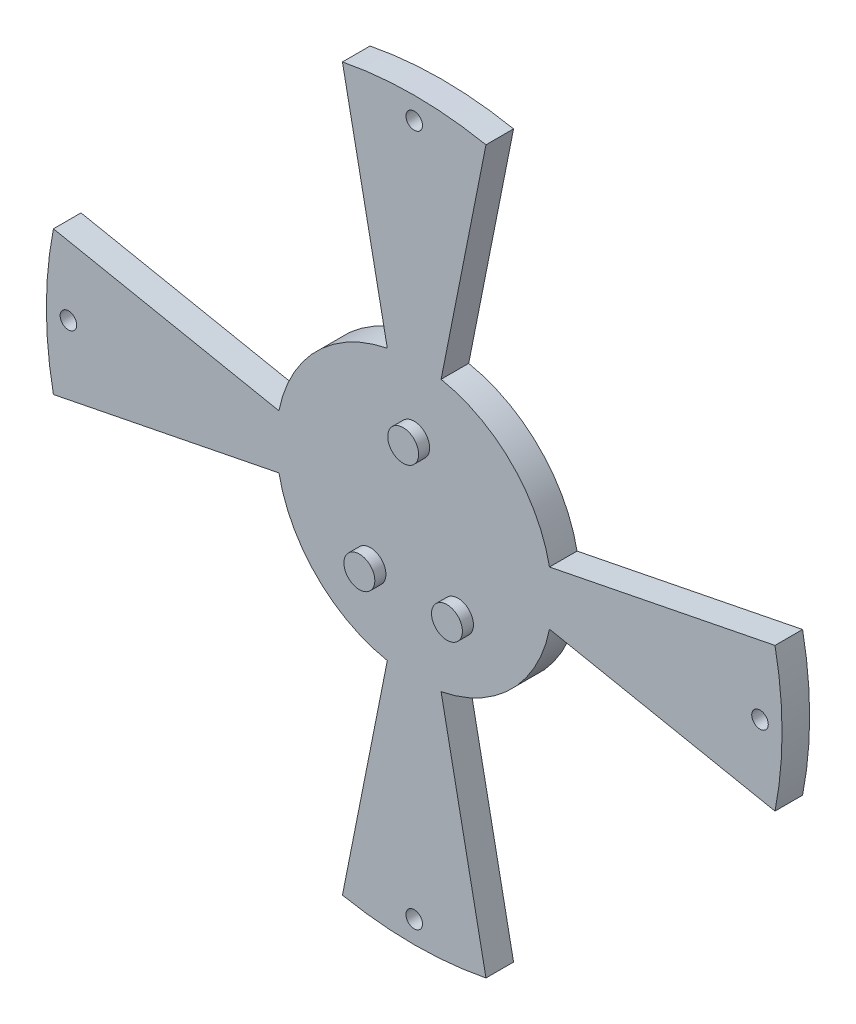
SolidWorks part; units mm, degrees
ref_plane "Front" through (0, 0, 0) normal (0, 0, 1) x (1, 0, 0)
ref_plane "Top" through (0, 0, 0) normal (0, 1, 0) x (1, 0, 0)
ref_plane "Right" through (0, 0, 0) normal (1, 0, 0) x (0, 0, -1)
sketch "Sketch1" plane through (0, 0, 0) normal (0, 0, 1) x (1, 0, 0)
  circle A0 centre (0, 0) radius 25
extrude "Extrude1" add sketch "Sketch1" along normal blind 5
sketch "Sketch4" plane through (0, 0, 5) normal (0, 0, 1) x (1, 0, 0)
  line L0 (4.044, 20.331) -> (-4.044, -20.331) construction
  line L1 (-4.044, 20.331) -> (4.044, -20.331) construction
  line L2 (-20.331, 4.044) -> (20.331, -4.044) construction
  line L3 (20.331, 4.044) -> (-20.331, -4.044) construction
  line L4 (-13.0074, 65.3939) -> (-4.6821, 23.5389)
  line L5 (13.0074, 65.3939) -> (4.6821, 23.5389)
  line L6 (65.3939, 13.0074) -> (23.5389, 4.6821)
  line L7 (65.3939, -13.0074) -> (23.5389, -4.6821)
  line L8 (4.6821, -23.5389) -> (13.0074, -65.3939)
  line L9 (-13.0074, -65.3939) -> (-4.6821, -23.5389)
  line L10 (-23.5389, -4.6821) -> (-65.3939, -13.0074)
  line L11 (-65.3939, 13.0074) -> (-23.5389, 4.6821)
  circle A0 centre (0, 20.73) radius 0.7 construction
  circle A1 centre (0, -20.73) radius 0.7 construction
  circle A2 centre (20.73, 0) radius 0.7 construction
  circle A3 centre (-20.73, 0) radius 0.7 construction
  circle A4 centre (-14.658, 14.658) radius 0.7 construction
  circle A5 centre (14.658, 14.658) radius 0.7 construction
  circle A6 centre (14.658, -14.658) radius 0.7 construction
  circle A7 centre (-14.658, -14.658) radius 0.7 construction
  circle A8 centre (19.152, 7.933) radius 0.7 construction
  circle A9 centre (7.933, 19.152) radius 0.7 construction
  circle A10 centre (19.152, -7.933) radius 0.7 construction
  circle A11 centre (7.933, -19.152) radius 0.7 construction
  circle A12 centre (-7.933, 19.152) radius 0.7 construction
  circle A13 centre (-19.152, 7.933) radius 0.7 construction
  circle A14 centre (-19.152, -7.933) radius 0.7 construction
  circle A15 centre (-7.933, -19.152) radius 0.7 construction
  circle A16 centre (20.331, 4.044) radius 0.7 construction
  circle A17 centre (20.331, -4.044) radius 0.7 construction
  circle A18 centre (4.044, -20.331) radius 0.7 construction
  circle A19 centre (-4.044, -20.331) radius 0.7 construction
  circle A20 centre (4.044, 20.331) radius 0.7 construction
  circle A21 centre (-4.044, 20.331) radius 0.6677 construction
  circle A22 centre (-20.331, 4.044) radius 0.7 construction
  circle A23 centre (-20.331, -4.044) radius 0.7 construction
  circle A24 centre (17.236, 11.516) radius 0.7 construction
  circle A25 centre (11.516, 17.236) radius 0.7 construction
  circle A26 centre (17.236, -11.516) radius 0.7 construction
  circle A27 centre (11.516, -17.236) radius 0.7 construction
  circle A28 centre (-11.516, -17.236) radius 0.7 construction
  circle A29 centre (-17.236, -11.516) radius 0.7 construction
  circle A30 centre (-17.236, 11.516) radius 0.7 construction
  circle A31 centre (-11.516, 17.236) radius 0.7 construction
  circle A32 centre (0, 17.555) radius 0.7 construction
  circle A33 centre (17.555, 0) radius 0.7 construction
  circle A34 centre (0, -17.555) radius 0.7 construction
  circle A35 centre (-17.555, 0) radius 0.7 construction
  circle A36 centre (-12.413, 12.413) radius 0.7 construction
  circle A37 centre (12.413, 12.413) radius 0.7 construction
  circle A38 centre (12.413, -12.413) radius 0.7 construction
  circle A39 centre (-12.413, -12.413) radius 0.7 construction
  circle A40 centre (-16.218, 6.718) radius 0.7 construction
  circle A41 centre (16.218, 6.718) radius 0.7 construction
  circle A42 centre (16.218, -6.718) radius 0.7 construction
  circle A43 centre (-16.218, -6.718) radius 0.7 construction
  circle A44 centre (6.718, 16.218) radius 0.7 construction
  circle A45 centre (6.718, -16.218) radius 0.7 construction
  circle A46 centre (-6.718, -16.218) radius 0.7 construction
  circle A47 centre (-6.718, 16.218) radius 0.7 construction
  circle A48 centre (0, 0) radius 60 construction
  circle A49 centre (0, 0) radius 66.675 construction
  circle A50 centre (0, 0) radius 24 construction
  arc A51 (23.5389, 4.6821) -> (23.5389, -4.6821) centre (0, 0) cw
  arc A52 (65.3939, 13.0074) -> (65.3939, -13.0074) centre (0, 0) cw
  arc A53 (4.6821, -23.5389) -> (-4.6821, -23.5389) centre (0, 0) cw
  arc A54 (13.0074, -65.3939) -> (-13.0074, -65.3939) centre (0, 0) cw
  arc A55 (-23.5389, -4.6821) -> (-23.5389, 4.6821) centre (0, 0) cw
  arc A56 (-65.3939, -13.0074) -> (-65.3939, 13.0074) centre (0, 0) cw
  arc A57 (-4.6821, 23.5389) -> (4.6821, 23.5389) centre (0, 0) cw
  arc A58 (-13.0074, 65.3939) -> (13.0074, 65.3939) centre (0, 0) cw
  circle A59 centre (62.675, 0) radius 1.5
  circle A60 centre (0, 62.675) radius 1.5
  circle A61 centre (0, -62.675) radius 1.5
  circle A62 centre (-62.675, 0) radius 1.5
  point P125 (-62.675, 0)
  point P126 (0, 62.675)
  point P127 (62.675, 0)
  point P128 (0, -62.675)
extrude "Extrude2" add sketch "Sketch4" against normal blind 5
sketch "Sketch6" plane through (0, 0, 5) normal (0, 0, 1) x (1, 0, 0)
  circle A0 centre (-7.9375, -11.1125) radius 2.8
  circle A1 centre (7.9375, -11.1125) radius 2.8
  circle A2 centre (0, 12.7) radius 2.8
extrude "Extrude4" add sketch "Sketch6" along normal blind 2
